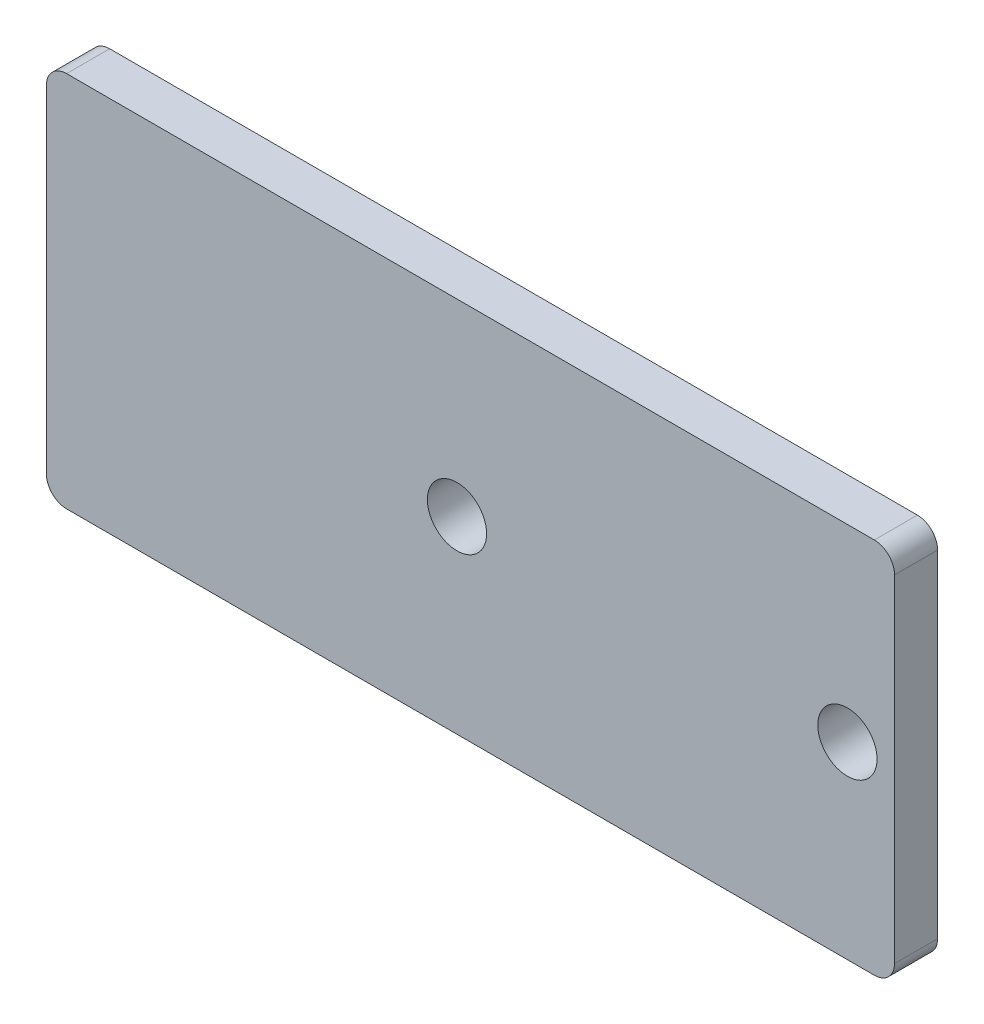
SolidWorks part; units mm, degrees
material "FR4_stuffedProtoboard"
ref_plane "Front Plane" through (0, 0, 0) normal (0, 0, 1) x (1, 0, 0)
ref_plane "Top Plane" through (0, 0, 0) normal (0, 1, 0) x (1, 0, 0)
ref_plane "Right Plane" through (0, 0, 0) normal (1, 0, 0) x (0, 0, -1)
sketch "Model" plane through (0, 0, 0) normal (0, 0, 1) x (1, 0, 0)
  line L0 (-15, -7) -> (15, -7)
  line L1 (15.75, -6.25) -> (15.75, 6.25)
  line L2 (15, 7) -> (-15, 7)
  line L3 (-15.75, 6.25) -> (-15.75, -6.25)
  arc A0 (15.75, 6.25) -> (15, 7) centre (15, 6.25) ccw
  arc A1 (15, -7) -> (15.75, -6.25) centre (15, -6.25) ccw
  arc A2 (-15.75, -6.25) -> (-15, -7) centre (-15, -6.25) ccw
  arc A3 (-15, 7) -> (-15.75, 6.25) centre (-15, 6.25) ccw
  circle A4 centre (-0.5, 0) radius 1.1
  circle A5 centre (14, 0) radius 1.1
  point P23 (0, 7)
  point P24 (15.75, 0)
  dimension "D3" = 0.75
  dimension "D7" = 0.75
  dimension "D8" = 2.2
  dimension "D9" = 2.2
  dimension "D1" = 30
  dimension "D2" = 12.5
  dimension "D4" = 6.25
  dimension "D5" = 14.5
  dimension "D6" = 1.75
  dimension "D10" = 0.75
extrude "Boss-Extrude1" add sketch "Model" along normal mid plane 1.6
sketch "Sketch1" plane through (0, 0, -0.8) normal (0, 0, 1) x (1, 0, 0)
  line L0 (15, 7) -> (-15, 7) construction
  line L1 (-13.75, 5) -> (-3.75, 5)
  line L2 (-13.75, 5) -> (-13.75, -5)
  line L3 (-13.75, -5) -> (-3.75, -5)
  line L4 (-3.75, 5) -> (-3.75, -5)
  line L5 (-15.75, 6.25) -> (-15.75, -6.25) construction
  dimension "D1" = 2
  dimension "D2" = 2
  dimension "D3" = 10
  dimension "D4" = 10
